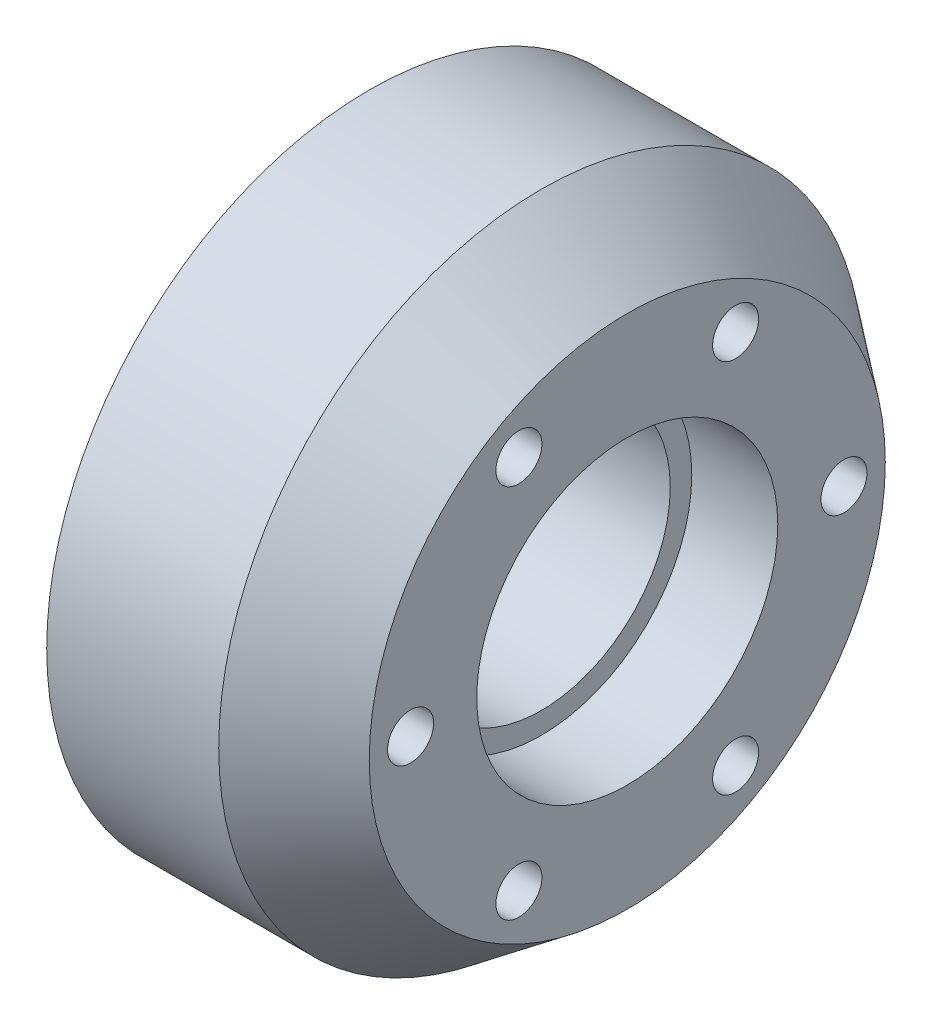
SolidWorks part; units mm, degrees
ref_plane "Front" through (0, 0, 0) normal (0, 0, 1) x (1, 0, 0)
ref_plane "Top" through (0, 0, 0) normal (0, 1, 0) x (1, 0, 0)
ref_plane "Right" through (0, 0, 0) normal (1, 0, 0) x (0, 0, -1)
sketch "Sketch1" plane through (0, 0, 0) normal (0, 0, 1) x (1, 0, 0)
  line L0 (0, 23.8125) -> (0, 9.525)
  line L1 (0, 9.525) -> (12.7, 9.525)
  line L2 (12.7, 9.525) -> (12.7, 11.1125)
  line L3 (12.7, 11.1125) -> (19.05, 11.1125)
  line L4 (19.05, 11.1125) -> (19.05, 19.05)
  line L5 (19.05, 19.05) -> (12.7, 23.8125)
  line L6 (12.7, 23.8125) -> (0, 23.8125)
  line L7 (0, 0) -> (-10.95, 0) construction
  dimension "D1" = 19.05
  dimension "D2" = 47.625
  dimension "D3" = 38.1
  dimension "D4" = 12.7
  dimension "D5" = 19.05
  dimension "D6" = 6.35
  dimension "D7" = 22.225
revolve "Revolve1" add sketch "Sketch1" angle 360 about L7
sketch "Sketch2" plane through (0, 0, 0) normal (0, 1, 0) x (1, 0, 0)
  line L0 (0, 0) -> (24.0323, 0) construction
  line L1 (19.05, 16) -> (23.214, 16) construction
  line L2 (19.05, -19.05) -> (19.05, 19.05) construction
  line L3 (19.05, 16) -> (0, 16)
  line L4 (0, 23.8125) -> (0, -23.8125) construction
  line L5 (0, 16) -> (0, 19.25)
  line L6 (0, 19.25) -> (12.7, 19.25)
  line L7 (12.7, 19.25) -> (12.7, 17.7)
  line L8 (12.7, 17.7) -> (19.05, 17.7)
  line L9 (19.05, 17.7) -> (19.05, 16)
  dimension "D1" = 3.4
  dimension "D2" = 6.5
  dimension "D3" = 6.35
  dimension "D4" = 32
revolve "Cut-Revolve1" cut sketch "Sketch2" angle 360 about L1
sketch "Sketch3" plane through (0, 0, 0) normal (0, 0, 1) x (1, 0, 0)
  line L0 (0, 19.05) -> (11.6666, 19.05)
  line L1 (0, 23.8125) -> (0, -23.8125) construction
  line L2 (11.6666, 19.05) -> (9.525, 22.225)
  line L3 (9.525, 22.225) -> (0, 22.225)
  line L4 (0, 22.225) -> (0, 19.05)
  line L5 (0, 19.05) -> (-4.5359, 19.05) construction
  line L6 (0, 0) -> (8.7066, 0) construction
  dimension "D1" = 6.35
  dimension "D2" = 112
  dimension "D3" = 38.1
  dimension "D4" = 9.525
revolve "Cut-Revolve2" cut sketch "Sketch3" angle 360 about L5
pattern_circular "CirPattern1" count 6 over 360 about axis through (0, 0, 0) along (1, 0, 0) of "Cut-Revolve2", "Cut-Revolve1"
